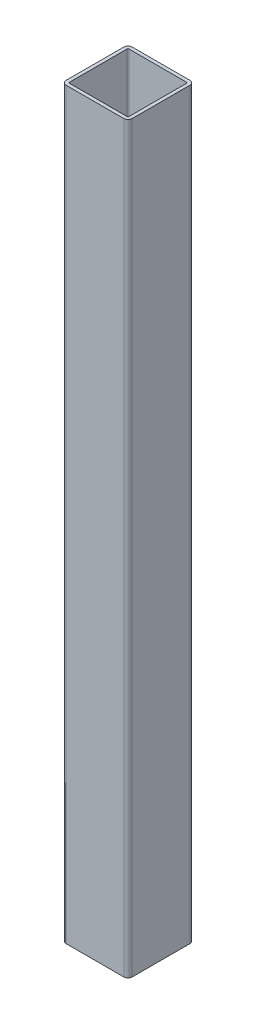
SolidWorks part; units mm, degrees
ref_plane "Спереди" through (0, 0, 0) normal (0, 0, 1) x (1, 0, 0)
ref_plane "Сверху" through (0, 0, 0) normal (0, 1, 0) x (1, 0, 0)
ref_plane "Справа" through (0, 0, 0) normal (1, 0, 0) x (0, 0, -1)
sketch "Эскиз1" plane through (0, 0, 0) normal (0, 1, 0) x (1, 0, 0)
  line L1 (-35, 40) -> (35, 40)
  line L2 (-40, 35) -> (-40, -35)
  line L3 (-35, -40) -> (35, -40)
  line L4 (40, 35) -> (40, -35)
  line L5 (-40, 40) -> (40, -40) construction
  line L6 (-40, -40) -> (40, 40) construction
  arc A0 (-40, -35) -> (-35, -40) centre (-35, -35) ccw
  arc A1 (35, -40) -> (40, -35) centre (35, -35) ccw
  arc A2 (35, 40) -> (40, 35) centre (35, 35) cw
  arc A3 (-35, 40) -> (-40, 35) centre (-35, 35) ccw
  point P0 (0, 0)
  dimension "D1" = 5
extrude "Вытянуть-Тонкостенный1" add sketch "Эскиз1" along normal blind 900 thin thin type one direction reverse wall 4
